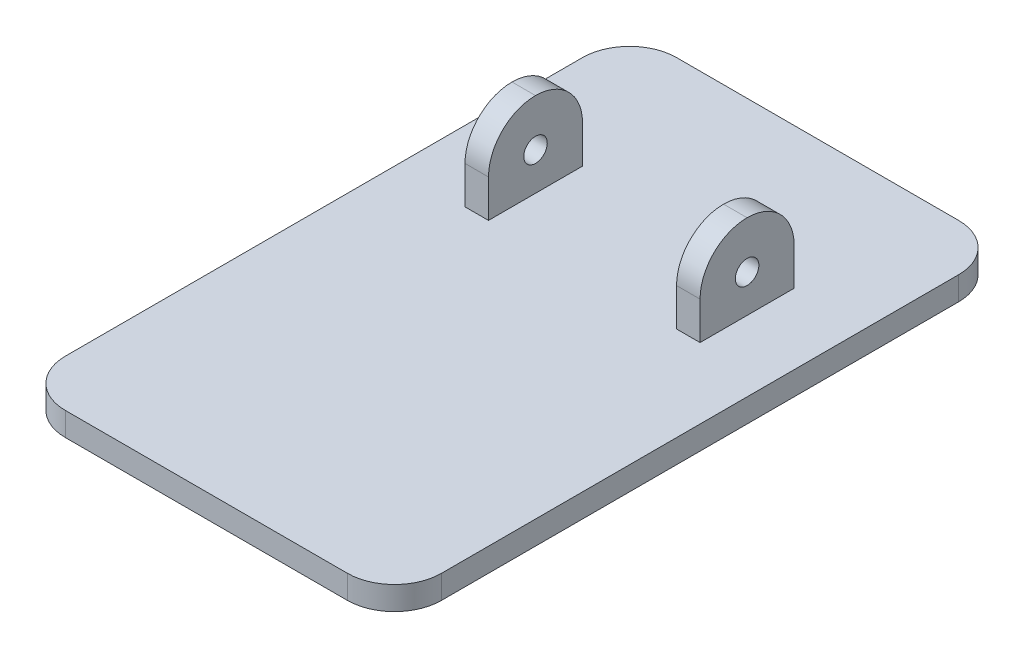
SolidWorks part; units mm, degrees
ref_plane "Płaszczyzna przednia" through (0, 0, 0) normal (0, 0, 1) x (1, 0, 0)
ref_plane "Płaszczyzna górna" through (0, 0, 0) normal (0, 1, 0) x (1, 0, 0)
ref_plane "Płaszczyzna prawa" through (0, 0, 0) normal (1, 0, 0) x (0, 0, -1)
sketch "Szkic1" plane through (0, 0, 0) normal (0, 1, 0) x (1, 0, 0)
  line L1 (40, -65) -> (-40, -65)
  line L2 (40, -65) -> (40, 65)
  line L3 (40, 65) -> (-40, 65)
  line L4 (-40, -65) -> (-40, 65)
  line L5 (40, -65) -> (-40, 65) construction
  line L6 (40, 65) -> (-40, -65) construction
  point P0 (0, 0)
  point P6 (0, 0)
  dimension "D1" = 80
  dimension "D2" = 130
extrude "Dodanie-wyciągnięcie1" add sketch "Szkic1" along normal blind 5 contours L2 L1 L4 L3
fillet "Zaokrąglenie1" radius 10 4 edges at (-40, 2.5, 65) (40, 2.5, 65) (40, 2.5, -65) (-40, 2.5, -65)
sketch "Szkic2" plane through (0, 5, 0) normal (0, 1, 0) x (1, 0, 0)
  line L0 (0, 65) -> (0, -7.4215) construction
  line L2 (-40, 35) -> (51.8108, 35) construction
  line L4 (30, 65) -> (-30, 65) construction
  line L5 (-40, 35) -> (-25, 35)
  line L7 (-40, -55) -> (-40, 55) construction
  line L8 (40, 35) -> (25, 35)
  line L9 (40, -55) -> (40, 55) construction
  line L10 (-25, 35) -> (-25, 15)
  line L11 (-25, 15) -> (-20, 15)
  line L12 (-25, 35) -> (-20, 35)
  line L13 (-20, 35) -> (-20, 15)
  line L14 (25, 35) -> (25, 15)
  line L15 (25, 15) -> (20, 15)
  line L16 (20, 15) -> (20, 35)
  line L17 (20, 35) -> (25, 35)
  line L18 (-20, 25) -> (20, 25) construction
  dimension "D1" = 30
  dimension "D2" = 15
  dimension "D3" = 15
  dimension "D4" = 20
  dimension "D5" = 5
  dimension "D6" = 40
extrude "Dodanie-wyciągnięcie2" add sketch "Szkic2" along normal blind 18 contours L13 L12 L10 L11 | L17 L16 L15 L14 region at (-22.5, 5, -25) region at (22.5, 5, -25)
fillet "Zaokrąglenie2" radius 10 4 edges at (22.5, 23, -15) (22.5, 23, -35) (-22.5, 23, -15) (-22.5, 23, -35)
ref_plane "Płaszczyzna1" through (-25, 0, 0) normal (-1, 0, 0) x (0, 0, 1)
sketch "Szkic3" plane through (-25, 0, 0) normal (-1, 0, 0) x (0, 0, 1)
  line L0 (-35, 13) -> (-15, 13) construction
  line L1 (-25, 5) -> (-25, 23) construction
  line L2 (-35, 5) -> (-15, 5) construction
  circle A0 centre (-25, 13) radius 2.5
  point P11 (0, 0)
  dimension "D1" = 5
  dimension "D2" = 8
extrude "Wytnij-wyciągnięcie1" cut sketch "Szkic3" against normal blind 100
